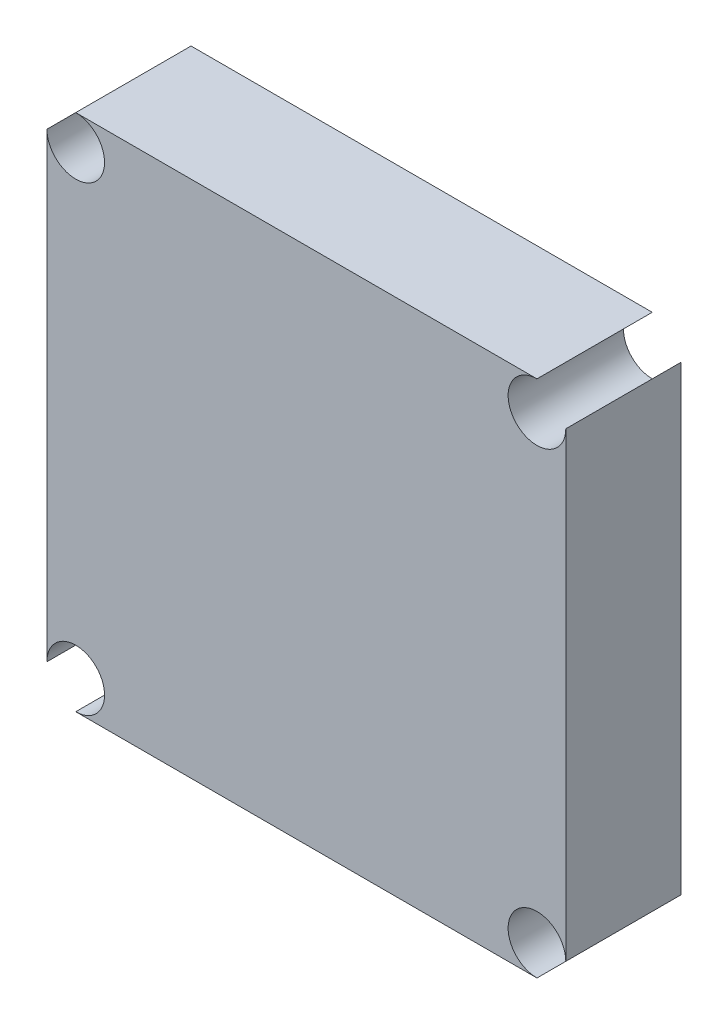
SolidWorks part; units mm, degrees
ref_plane "Front Plane" through (0, 0, 0) normal (0, 0, 1) x (1, 0, 0)
ref_plane "Top Plane" through (0, 0, 0) normal (0, 1, 0) x (1, 0, 0)
ref_plane "Right Plane" through (0, 0, 0) normal (1, 0, 0) x (0, 0, -1)
sketch "Sketch1" plane through (0, 0, 0) normal (0, 0, 1) x (1, 0, 0)
  line L1 (-18, -18) -> (18, -18)
  line L2 (-18, -18) -> (-18, 18)
  line L3 (-18, 18) -> (18, 18)
  line L4 (18, -18) -> (18, 18)
  line L5 (-18, -18) -> (18, 18) construction
  line L6 (-18, 18) -> (18, -18) construction
  line L7 (-16, -16) -> (16, -16) construction
  line L8 (-16, -16) -> (-16, 16) construction
  line L9 (-16, 16) -> (16, 16) construction
  line L10 (16, -16) -> (16, 16) construction
  line L11 (-16, -16) -> (16, 16) construction
  line L12 (-16, 16) -> (16, -16) construction
  circle A0 centre (-16, 16) radius 2
  circle A1 centre (16, 16) radius 2
  circle A2 centre (16, -16) radius 2
  circle A3 centre (-16, -16) radius 2
  point P0 (0, 0)
  point P6 (0, 0)
  point P15 (16, 0)
  dimension "D3" = 4
  dimension "D4" = 4
  dimension "D5" = 4
  dimension "D6" = 4
  dimension "D1" = 36
  dimension "D2" = 36
  dimension "D7" = 32
  dimension "D8" = 32
extrude "Boss-Extrude1" add sketch "Sketch1" along normal mid plane 8 contours A3 L1 A2 L4 A1 L3 A0 L2 region at (0, 0, 0)
